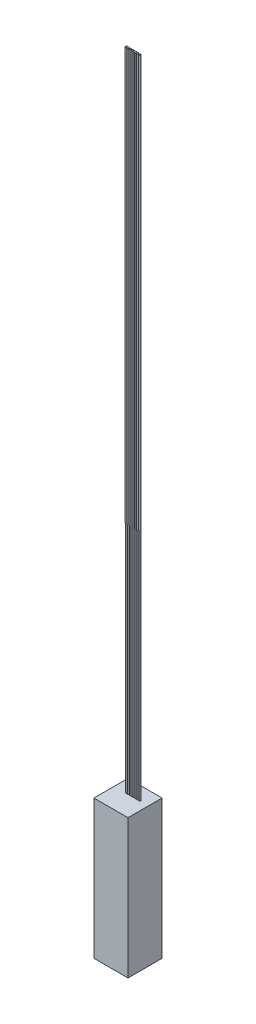
SolidWorks part; units mm, degrees
ref_plane "Front Plane" through (0, 0, 0) normal (0, 0, 1) x (1, 0, 0)
ref_plane "Top Plane" through (0, 0, 0) normal (0, 1, 0) x (1, 0, 0)
ref_plane "Right Plane" through (0, 0, 0) normal (1, 0, 0) x (0, 0, -1)
sketch "Fiber_Block_sketch" plane through (0, 0, 0) normal (0, 1, 0) x (1, 0, 0)
  line L1 (0, 0) -> (2.4786, 0)
  line L2 (0, 0) -> (0, -2.4786)
  line L3 (0, -2.4786) -> (2.4786, -2.4786)
  line L4 (2.4786, 0) -> (2.4786, -2.4786)
  dimension "D1" = 2.4786
extrude "Fiber_Block" add sketch "Fiber_Block_sketch" along normal blind 10.1
sketch "Fiber_Sketch" plane through (0, 10.1, 0) normal (0, 1, 0) x (1, 0, 0)
  line L0 (2.4786, 0) -> (0, 0) construction
  line L1 (0, 0) -> (0, -2.4786) construction
  circle A0 centre (0.85, -0.968) radius 0.05
  circle A1 centre (0.99, -0.968) radius 0.05
  circle A2 centre (1.13, -0.968) radius 0.05
  circle A3 centre (1.27, -0.968) radius 0.05
  circle A4 centre (1.41, -0.968) radius 0.05
  circle A5 centre (1.55, -0.968) radius 0.05
  circle A6 centre (1.69, -0.968) radius 0.05
  circle A7 centre (0.85, -0.968) radius 0.065
  circle A8 centre (0.99, -0.968) radius 0.065
  circle A9 centre (1.13, -0.968) radius 0.065
  circle A10 centre (1.27, -0.968) radius 0.065
  circle A11 centre (1.41, -0.968) radius 0.065
  circle A12 centre (1.55, -0.968) radius 0.065
  circle A13 centre (1.69, -0.968) radius 0.065
  circle A14 centre (1.83, -0.968) radius 0.065
  circle A15 centre (1.83, -0.968) radius 0.05
  dimension "D2" = 0.1
  dimension "D6" = 0.13
  dimension "D1" = 0.968
  dimension "D3" = 0.85
  dimension "D5" = 0.14
  dimension "D4" = 8
  dimension "D7" = 8
extrude "Fibers" add sketch "Fiber_Sketch" along normal blind 17 contours A15 | A6 | A5 | A4 | A3 | A2 | A0 | A1
extrude "Fiber_Shield" add sketch "Fiber_Sketch<3>" along normal blind 30 from surface separate body contours A7 A0 | A8 A1 | A9 A2 | A10 A3 | A11 A4 | A12 A5 | A13 A6 | A14 A15 | A15 | A6 | A5 | A4 | A3 | A0 | A1 | A2 region at (0.85, 10.1, 0.968) region at (0.99, 10.1, 0.968) region at (1.13, 10.1, 0.968) region at (1.27, 10.1, 0.968) region at (1.41, 10.1, 0.968) region at (1.55, 10.1, 0.968) region at (1.69, 10.1, 0.968) region at (0.7868, 10.1, 0.968) region at (0.9268, 10.1, 0.968) region at (1.0668, 10.1, 0.968) region at (1.2068, 10.1, 0.968) region at (1.3468, 10.1, 0.968) region at (1.4868, 10.1, 0.968) region at (1.6268, 10.1, 0.968) region at (1.7668, 10.1, 0.968) region at (1.83, 10.1, 0.968) starting at face at (1.69, 27.1, 1.018)
sketch "Fiber_Sketch<3>" plane through (0, 10.1, 0) normal (0, 1, 0) x (1, 0, 0) same geometry as "Fiber_Sketch"
